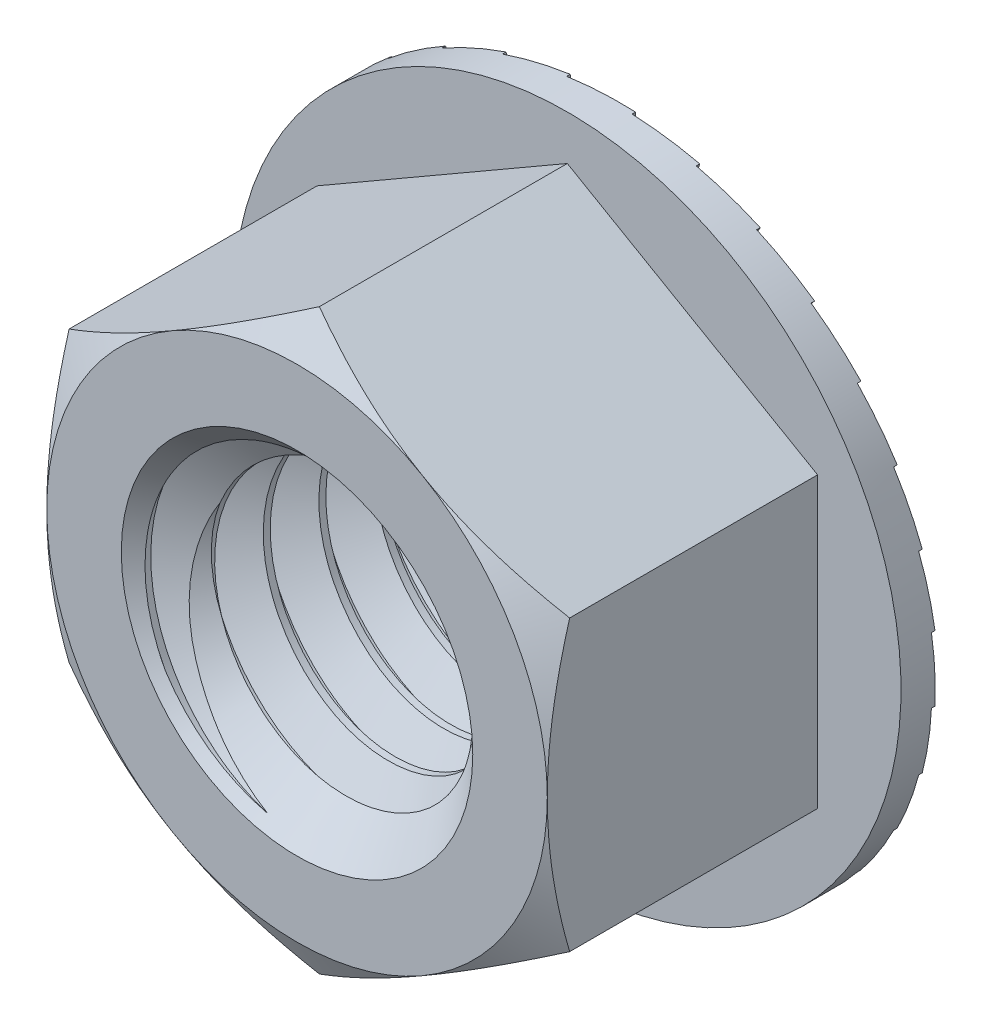
SolidWorks part; units mm, degrees
material "Plain Carbon Steel"
ref_plane "Front Plane" through (0, 0, 0) normal (0, 0, 1) x (1, 0, 0)
ref_plane "Top Plane" through (0, 0, 0) normal (0, 1, 0) x (1, 0, 0)
ref_plane "Right Plane" through (0, 0, 0) normal (1, 0, 0) x (0, 0, -1)
sketch "Sketch1" plane through (0, 0, 0) normal (0, 0, 1) x (1, 0, 0)
  line L1 (0, 8.2489) -> (-7.1438, 4.1244)
  line L2 (-7.1438, 4.1244) -> (-7.1438, -4.1244)
  line L3 (-7.1438, -4.1244) -> (0, -8.2489)
  line L4 (0, -8.2489) -> (7.1437, -4.1244)
  line L5 (7.1437, -4.1244) -> (7.1437, 4.1244)
  line L6 (7.1437, 4.1244) -> (0, 8.2489)
  circle A0 centre (0, 0) radius 7.1438 construction
  dimension "Hex" = 14.2875
extrude "Extrude1" add sketch "Sketch1" against normal blind 8.7312
sketch "Sketch13" plane through (0, 0, -8.7312) normal (0, 0, -1) x (-1, 0, 0)
  circle A0 centre (0, 0) radius 9.525
  dimension "Flange od" = 19.05
extrude "Extrude3" add sketch "Sketch13" against normal blind 1.016
sketch "Sketch2" plane through (0, 0, 0) normal (0, 0, 1) x (1, 0, 0)
  circle A0 centre (0, 0) radius 7.1438 construction
  circle A1 centre (0, 0) radius 7.1438
extrude "Cut-Extrude1" cut sketch "Sketch2" against normal through all draft 60 flip side to cut
sketch "Sketch4" plane through (0, 0, 0) normal (0, 0, 1) x (1, 0, 0)
  circle A0 centre (0, 0) radius 4.7625
  dimension "Thread Dia" = 9.525
extrude "Cut-Extrude3" cut sketch "Sketch4" against normal through all
sketch "Sketch7" plane through (0, 0, 0) normal (0, 0, 1) x (1, 0, 0)
  circle A4 centre (0, 0) radius 5.0165
  circle A5 centre (0, 0) radius 5.0165
  dimension "D1" = 0.254
sketch "Sketch8" plane through (0, 0, -8.7312) normal (0, 0, -1) x (-1, 0, 0)
  circle A1 centre (0, 0) radius 5.0165
  circle A2 centre (0, 0) radius 5.0165 construction
sketch "Sketch5" plane through (0, 0, 0) normal (0, 0, 1) x (1, 0, 0)
  circle A0 centre (0, 0) radius 4.7625 construction
  circle A1 centre (0, 0) radius 4.7625
curve "Helix/Spiral1" pitch 1.5875 height 10.3187 turns 6.5 parameters "pitch"=1.5875
sketch "Sketch9" plane through (0, 0, 0) normal (1, 0, 0) x (0, 0, -1)
  line L0 (-0.7937, 4.7625) -> (-0.5953, 4.7625)
  line L1 (-0.5953, 4.7625) -> (0, 3.7314)
  line L2 (-0.7937, 4.7625) -> (-1.3891, 3.7314)
  line L3 (-1.3891, 3.7314) -> (0, 3.7314)
  line L4 (-0.6945, 4.7625) -> (-0.6945, 3.7314) construction
  line L5 (-1.0914, 4.2469) -> (-0.2977, 4.2469) construction
  line L7 (0, 3.7314) -> (0, 4.7625) construction
  line L8 (0, 4.7625) -> (0, -4.7625) construction
  dimension "D1" = 0.1984
  dimension "D2" = 0.7937
  dimension "D3" = 60
sketch "Sketch12" plane through (0, 0, 0) normal (0, 0, 1) x (1, 0, 0)
  circle A0 centre (0, 0) radius 3.7314
  circle A1 centre (0, 0) radius 4.7625 construction
  circle A2 centre (0, 0) radius 4.7625
extrude "Extrude2" add sketch "Sketch12" against normal up to surface (8.7312 mm away)
sweep "Cut-Sweep1" cut profiles "Sketch9" path "Helix/Spiral1"
extrude "Cut-Extrude6" cut sketch "Sketch7" against normal through all draft 45
extrude "Cut-Extrude7" cut sketch "Sketch8" against normal through all draft 45
sketch "Sketch14" plane through (0, 0, -8.7312) normal (0, 0, -1) x (-1, 0, 0)
  circle A4 centre (0, 0) radius 7.0485
  circle A5 centre (0, 0) radius 7.0485
  dimension "D1" = 2.032
extrude "Cut-Extrude8" cut sketch "Sketch14" against normal blind 0.1016 flip side to cut
sketch "Sketch15" plane through (0, 0, -8.6296) normal (0, 0, -1) x (-1, 0, 0)
  line L0 (-0.6909, 7.0146) -> (-0.9336, 9.4791)
  line L1 (0.6909, 7.0146) -> (0.9336, 9.4791)
  line L2 (0, 0) -> (0.6909, 7.0146) construction
  line L3 (0, 0) -> (-0.6909, 7.0146) construction
  circle A0 centre (0, 0) radius 9.525 construction
  circle A1 centre (0, 0) radius 7.0485 construction
  arc A2 (0.9336, 9.4791) -> (-0.9336, 9.4791) centre (0, 0) ccw
  arc A3 (0.6909, 7.0146) -> (-0.6909, 7.0146) centre (0, 0) ccw
  dimension "D1" = 11.25
extrude "Extrude4" add sketch "Sketch15" along normal up to surface (0.1016 mm away) separate body up to face at (-5.0165, 0, -8.7312)
sketch "Sketch16" plane through (0, 0, 0) normal (0, 1, 0) x (1, 0, 0)
  line L0 (-0.9336, 8.6296) -> (0.9336, 8.7312)
  line L4 (-0.9336, 8.6296) -> (0.9336, 8.6296)
  line L5 (0.9336, 8.6296) -> (0.9336, 8.7312)
  line L6 (0.9336, 8.7312) -> (-0.9336, 8.7312)
  line L7 (-0.9336, 8.7312) -> (-0.9336, 8.6296)
  line L8 (-0.9336, 8.6296) -> (0.9336, 8.6296) construction
  line L9 (0.9336, 8.6296) -> (0.9336, 8.7312) construction
  line L10 (0.9336, 8.7312) -> (-0.9336, 8.7312)
  line L11 (-0.9336, 8.7312) -> (-0.9336, 8.6296)
  dimension "D1" = 0
extrude "Cut-Extrude9" cut sketch "Sketch16" along normal through all
pattern_circular "CirPattern1" count 32 over 360 about axis through (0, 0, 0) along (0, 0, 1) of bodies 119
combine bodies "Combine1" operation type add bodies to combine 117 119 120 121 122 123 124 125 126 127 128 129 130 131 132 133 134 135 136 137 139 140 141 142 143 144 145 146 147 148 149 150 151
sketch "Sketch17" plane through (0, 0, 0) normal (1, 0, 0) x (0, 0, -1)
  line L0 (8.7312, 9.525) -> (8.7313, -9.525) construction
  line L1 (7.7153, 9.525) -> (7.7153, -9.525) construction
  dimension "D1" = 1.016
sketch "Sketch18" plane through (0, 0, -7.7153) normal (0, 0, 1) x (1, 0, 0)
  circle A0 centre (0, 0) radius 9.525
  circle A1 centre (0, 0) radius 9.525 construction
equation "\"D2@Sketch9\" = \"pitch@Helix/Spiral1\"*.5"
equation "\"D3@Helix/Spiral1\" = \"pitch@Helix/Spiral1\"+\"Height@Extrude1\""
equation "\"D1@Sketch9\" = \"pitch@Helix/Spiral1\"*.125"
equation "\"D1@Cut-Extrude8\" = \"flange thickness@Extrude3\"*.1"
equation "\"D1@Sketch17\" = \"flange thickness@Extrude3\""
